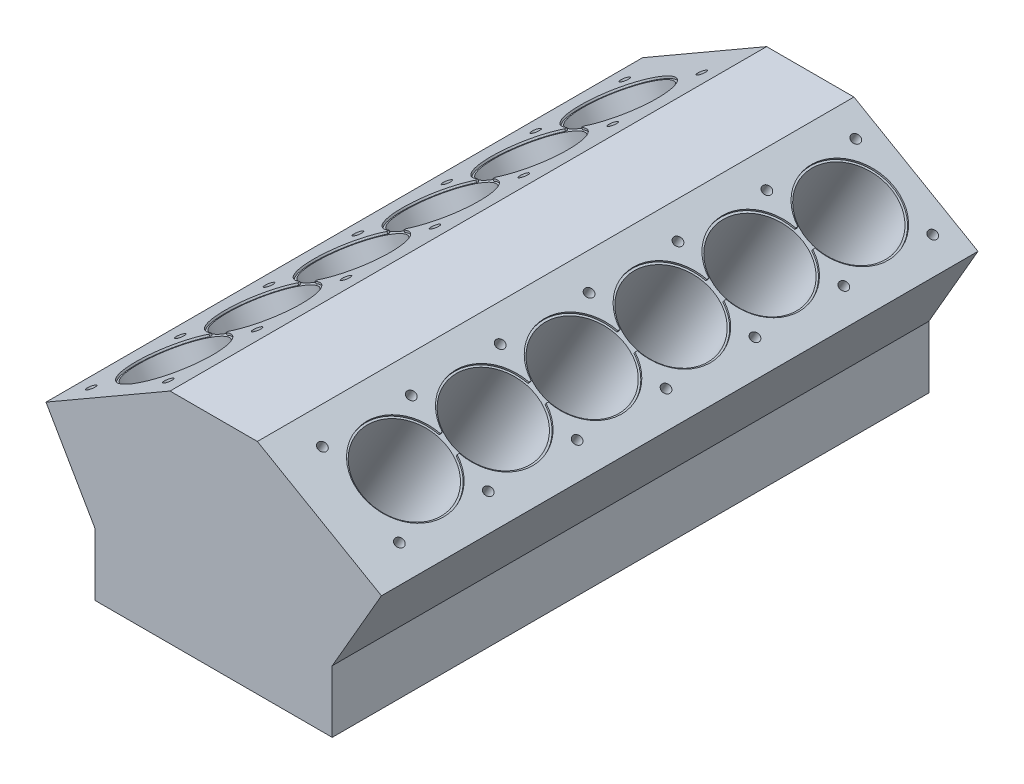
SolidWorks part; units mm, degrees
material "1060 Alloy"
ref_plane "Front Plane" through (0, 0, 0) normal (0, 0, 1) x (1, 0, 0)
ref_plane "Top Plane" through (0, 0, 0) normal (0, 1, 0) x (1, 0, 0)
ref_plane "Right Plane" through (0, 0, 0) normal (1, 0, 0) x (0, 0, -1)
sketch "Sketch1" plane through (0, 0, 0) normal (0, 0, 1) x (1, 0, 0)
  line L0 (0, 0) -> (120, 0)
  line L1 (120, 0) -> (120, 62.8461)
  line L2 (120, 62.8461) -> (169.7868, 149.0794)
  line L3 (169.7868, 149.0794) -> (44.2132, 221.5794)
  line L4 (44.2132, 221.5794) -> (0, 221.5794)
  line L5 (0, 221.5794) -> (0, 0)
  line L6 (0, 0) -> (107, 185.3294) construction
  dimension "D1" = 120
  dimension "D2" = 150
  dimension "D3" = 145
  dimension "D4" = 214
extrude "Boss-Extrude1" add sketch "Sketch1" along normal mid plane 604
mirror "Mirror1" about plane through (0, 0, 0) normal (1, 0, 0) of bodies 101
sketch "Sketch2" plane through (-107, 185.3294, 0) normal (0.5, -0.866, 0) x (-0.866, -0.5, 0)
  line L0 (72.5, 302) -> (-72.5, 302) construction
  circle A0 centre (0, 215) radius 43
  dimension "D1" = 86
  dimension "D2" = 87
extrude "Cut-Extrude1" cut sketch "Sketch2" along normal blind 154
sketch "Sketch3" plane through (107, 185.3294, 0) normal (0.5, 0.866, 0) x (0.866, -0.5, 0)
  line L0 (72.5, 302) -> (-72.5, 302) construction
  circle A0 centre (0, 235) radius 43
  dimension "D1" = 86
  dimension "D2" = 67
extrude "Cut-Extrude2" cut sketch "Sketch3" against normal blind 154
pattern_linear "LPattern1" count 6 spacing 90 along (0, 0, 1) of "Cut-Extrude1", "Cut-Extrude2"
sketch "Sketch4" plane through (-107, 185.3294, 0) normal (-0.5, 0.866, 0) x (0.866, 0.5, 0)
  line L0 (-10, 171.1252) -> (-10, -191.1398) construction
  line L1 (-10, 171.1252) -> (-10, 168.9191)
  line L2 (10, 171.1252) -> (10, 168.8143)
  line L3 (-10, 81.066) -> (-10, 78.9045)
  line L4 (10, -191.1398) -> (10, 171.1252) construction
  line L5 (0, 215) -> (0, -235) construction
  line L7 (10, 81.1708) -> (10, 78.8296)
  line L8 (-10, -8.9194) -> (-10, -11.1101)
  line L9 (10, -8.8444) -> (10, -11.1553)
  line L10 (-10, -98.9047) -> (-10, -101.1466)
  line L11 (10, -98.8595) -> (10, -101.1186)
  line L12 (-10, -188.8681) -> (-10, -191.1398)
  line L13 (10, -188.8962) -> (10, -191.1398)
  arc A0 (-10, 168.9191) -> (-10, 81.066) centre (-0.2299, 124.9925) ccw
  arc A1 (10, 81.1708) -> (10, 168.8143) centre (-0.2299, 124.9925) ccw
  arc A2 (34.641, -209.5245) -> (41.8744, -244.774) centre (0, -235) ccw construction
  arc A5 (10, -8.8444) -> (10, 78.8296) centre (-0.1644, 34.9926) ccw
  arc A6 (10, -98.8595) -> (10, -11.1553) centre (-0.099, -55.0074) ccw
  arc A7 (10, -188.8962) -> (10, -101.1186) centre (0.0615, -145.0074) ccw
  circle A11 centre (0, 215) radius 45
  arc A12 (10, 171.1252) -> (-10, 171.1252) centre (0, 215) ccw
  arc A13 (-10, 78.9045) -> (-10, -8.9194) centre (-0.1644, 34.9926) ccw
  arc A14 (-10, -11.1101) -> (-10, -98.9047) centre (-0.099, -55.0074) ccw
  arc A15 (-10, -101.1466) -> (-10, -188.8681) centre (0.0615, -145.0074) ccw
  arc A16 (-10, -191.1398) -> (10, -191.1398) centre (0, -235) ccw
  circle A17 centre (0, 125) radius 43 construction
  point P0 (-10, 215)
  point P1 (-10, -235)
  point P15 (10, 215)
  point P16 (10, -235)
  dimension "D3" = 44.9857
  dimension "D4" = 0.0615
  dimension "D5" = 0.099
  dimension "D6" = 0.1644
  dimension "D7" = 0.2299
  dimension "D8" = 43.8143
  dimension "D1" = 20
  dimension "D9" = 46.0955
  dimension "D10" = 136.1101
  dimension "D11" = 226.1186
  dimension "D2" = 2
extrude "Cut-Extrude4" cut sketch "Sketch4" against normal blind 2
sketch "Sketch6" plane through (107, 185.3294, 0) normal (0.5, 0.866, 0) x (0.866, -0.5, 0)
  line L0 (-10, 191.1252) -> (-10, -171.1398) construction
  line L1 (-10, 191.1252) -> (-10, 188.9191)
  line L2 (10, 191.1252) -> (10, 188.8143)
  line L3 (-10, 101.066) -> (-10, 98.9045)
  line L4 (10, -171.1398) -> (10, 191.1252) construction
  line L5 (0, 235) -> (0, -215) construction
  line L6 (10, 101.1708) -> (10, 98.8296)
  line L7 (-10, 11.0806) -> (-10, 8.8899)
  line L8 (10, 11.1556) -> (10, 8.8447)
  line L9 (-10, -78.9047) -> (-10, -81.1466)
  line L10 (10, -78.8595) -> (10, -81.1186)
  line L11 (-10, -168.8681) -> (-10, -171.1398)
  line L12 (10, -168.8962) -> (10, -171.1398)
  arc A0 (-10, 188.9191) -> (-10, 101.066) centre (-0.2299, 144.9925) ccw
  arc A1 (10, 101.1708) -> (10, 188.8143) centre (-0.2299, 144.9925) ccw
  arc A2 (10, 11.1556) -> (10, 98.8296) centre (-0.1644, 54.9926) ccw
  arc A3 (10, -78.8595) -> (10, 8.8447) centre (-0.099, -35.0074) ccw
  arc A4 (10, -168.8962) -> (10, -81.1186) centre (0.0615, -125.0074) ccw
  arc A5 (10, 191.1252) -> (-10, 191.1252) centre (0, 235) ccw
  arc A6 (-10, 98.9045) -> (-10, 11.0806) centre (-0.1644, 54.9926) ccw
  arc A7 (-10, 8.8899) -> (-10, -78.9047) centre (-0.099, -35.0074) ccw
  arc A8 (-10, -81.1466) -> (-10, -168.8681) centre (0.0615, -125.0074) ccw
  arc A9 (-10, -171.1398) -> (10, -171.1398) centre (0, -215) ccw
  circle A10 centre (0, 145) radius 43 construction
  dimension "D2" = 44.9857
  dimension "D3" = 45
  dimension "D1" = 20
  dimension "D4" = 0.0615
  dimension "D5" = 10
  dimension "D6" = 0.099
  dimension "D7" = 0.1644
  dimension "D8" = 0.2299
  dimension "D9" = 43.8143
  dimension "D10" = 46.1252
  dimension "D11" = 46.0955
  dimension "D12" = 136.1101
  dimension "D13" = 226.1186
  dimension "D14" = 316.1398
extrude "Cut-Extrude5" cut sketch "Sketch6" against normal blind 2
hole_wizard "M10x1.0 Tapped Hole1" positions "Sketch7" profile "Sketch9" tap size "M10x1.0" standard "DIN"
sketch "Sketch7" plane through (-107, 185.3294, 0) normal (-0.5, 0.866, 0) x (0.866, 0.5, 0)
  line L0 (0, 215.5383) -> (0, 272.7266) construction
  point P0 (45, 260)
  point P16 (-45, 260)
  point P21 (45, 170)
  point P22 (-45, 170)
  point P23 (45, 80)
  point P24 (-45, 80)
  point P25 (45, -10)
  point P26 (-45, -10)
  point P27 (45, -100)
  point P28 (-45, -100)
  point P29 (45, -190)
  point P30 (-45, -190)
  point P31 (45, -280)
  point P32 (-45, -280)
  dimension "D1" = 45
  dimension "D2" = 45
  dimension "D3" = 7
sketch "Sketch9" plane through (-68.0289, 207.8294, -260) normal (0, 0, 1) x (-0.866, -0.5, 0)
  line L0 (0, 0) -> (0, 49.7039)
  line L1 (0, 49.7039) -> (4.5, 47)
  line L2 (4.5, 47) -> (4.5, 0)
  line L5 (4.5, 0) -> (0, 0)
  line L10 (0, 49.7039) -> (-4.5, 47) construction
  line L11 (0, -6.35) -> (0, 107.95) construction
  dimension "Tap Drill Dia." = 9
  dimension "Tap Drill Depth" = 47
  dimension "Drill Angle" = 118
cosmetic thread "Hole Thread1" parameters "D1"=20, "D2"=10
cosmetic thread "Hole Thread2" parameters "D1"=20, "D2"=10
cosmetic thread "Hole Thread3" parameters "D1"=20, "D2"=10
cosmetic thread "Hole Thread4" parameters "D1"=20, "D2"=10
cosmetic thread "Hole Thread5" parameters "D1"=20, "D2"=10
cosmetic thread "Hole Thread6" parameters "D1"=20, "D2"=10
cosmetic thread "Hole Thread7" parameters "D1"=20, "D2"=10
cosmetic thread "Hole Thread8" parameters "D1"=20, "D2"=10
cosmetic thread "Hole Thread9" parameters "D1"=20, "D2"=10
cosmetic thread "Hole Thread10" parameters "D1"=20, "D2"=10
cosmetic thread "Hole Thread11" parameters "D1"=20, "D2"=10
cosmetic thread "Hole Thread12" parameters "D1"=20, "D2"=10
cosmetic thread "Hole Thread13" parameters "D1"=20, "D2"=10
cosmetic thread "Hole Thread14" parameters "D1"=20, "D2"=10
hole_wizard "M10x1.0 Tapped Hole2" positions "Sketch10" profile "Sketch11" tap size "M10x1.0" standard "DIN"
sketch "Sketch10" plane through (107, 185.3294, 0) normal (0.5, 0.866, 0) x (0.866, -0.5, 0)
  arc A0 (10, 191.1252) -> (-10, 191.1252) centre (0, 235) ccw construction
  point P0 (-45, 280)
  dimension "D1" = 45
  dimension "D2" = 45
sketch "Sketch11" plane through (68.0289, 207.8294, -280) normal (0, 0, 1) x (-0.866, 0.5, 0)
  line L0 (0, 0) -> (0, 49.7039)
  line L1 (0, 49.7039) -> (4.5, 47)
  line L2 (4.5, 47) -> (4.5, 0)
  line L5 (4.5, 0) -> (0, 0)
  line L10 (0, 49.7039) -> (-4.5, 47) construction
  line L11 (0, -6.35) -> (0, 107.95) construction
  dimension "Tap Drill Dia." = 9
  dimension "Tap Drill Depth" = 47
  dimension "Drill Angle" = 118
pattern_linear "LPattern2" count 2 spacing 90 along (0.866, -0.5, 0) count 7 spacing 90 along (0, 0, 1) of "M10x1.0 Tapped Hole2"
